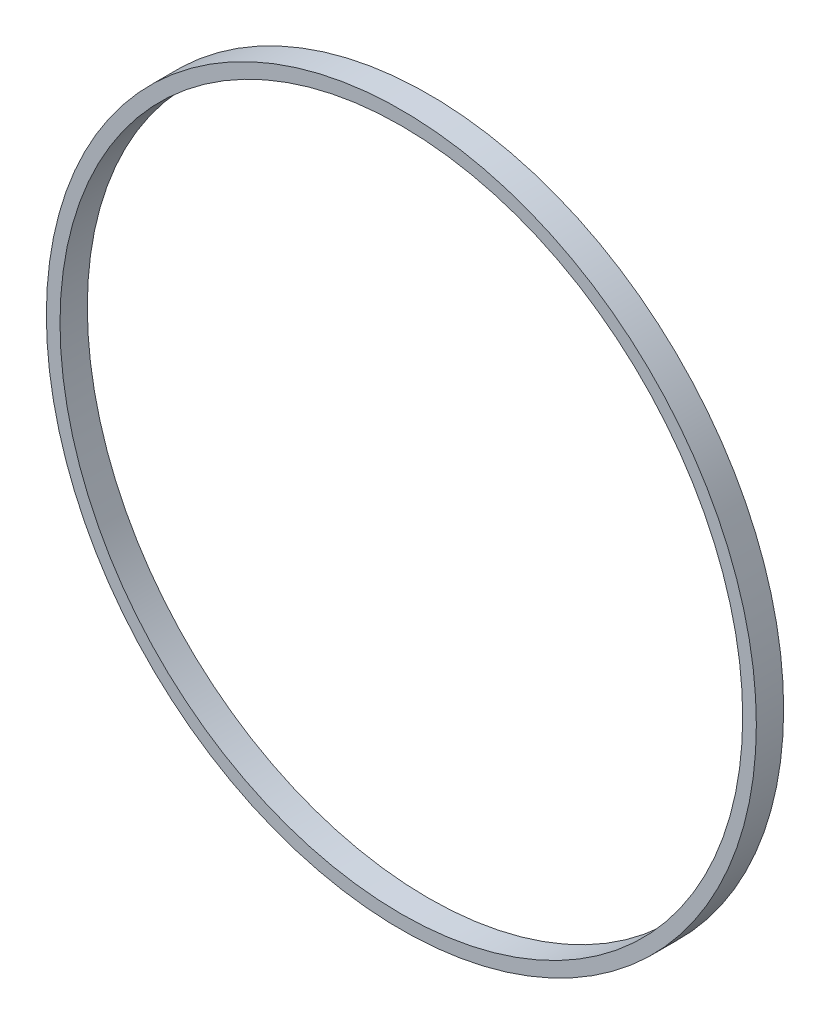
SolidWorks part; units mm, degrees
ref_plane "Front Plane" through (0, 0, 0) normal (0, 0, 1) x (1, 0, 0)
ref_plane "Top Plane" through (0, 0, 0) normal (0, 1, 0) x (1, 0, 0)
ref_plane "Right Plane" through (0, 0, 0) normal (1, 0, 0) x (0, 0, -1)
sketch "Sketch1" plane through (0, 0, 0) normal (0, 0, 1) x (1, 0, 0)
  line L0 (78.4818, 151.5744) -> (392.4092, 151.5744) construction
  circle A0 centre (0, 0) radius 66.04
  circle A1 centre (0, 0) radius 63.5
  point P4 (132.0118, 198.0891)
  point P7 (0, 0)
  dimension "D1" = 132.08
  dimension "D2" = 127
extrude "Boss-Extrude1" add sketch "Sketch1" along normal blind 5.08
